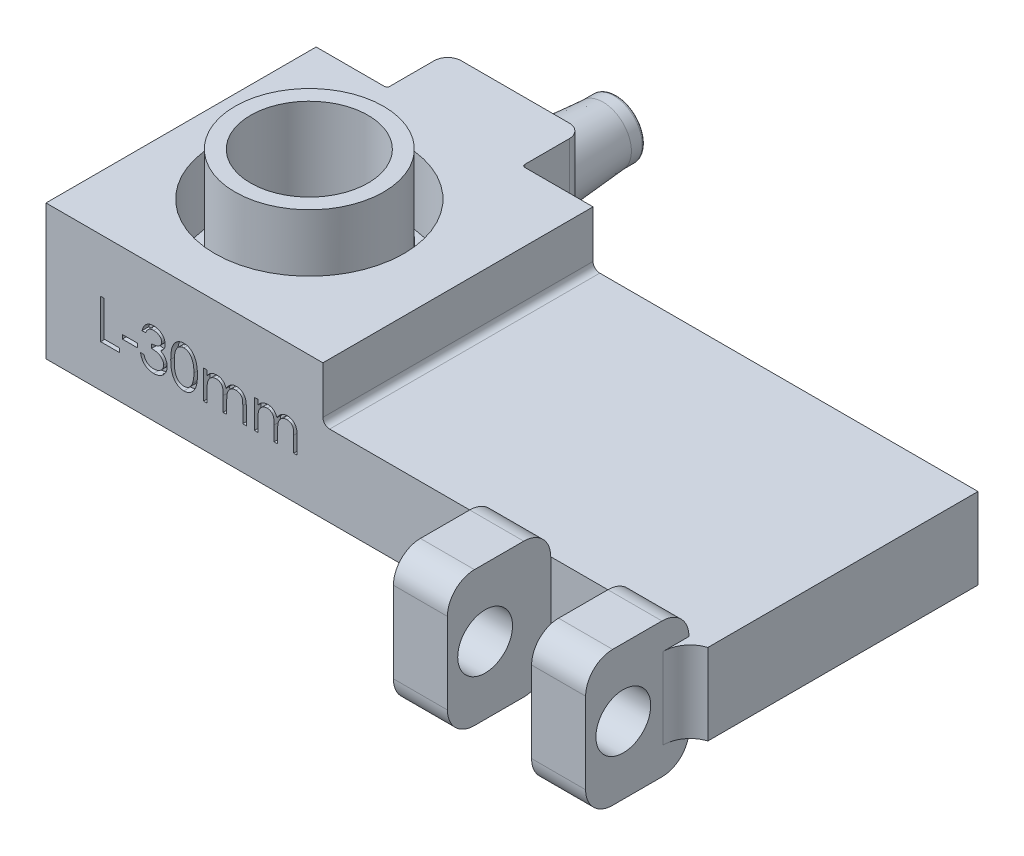
SolidWorks part; units mm, degrees
ref_plane "Front Plane" through (0, 0, 0) normal (0, 0, 1) x (1, 0, 0)
ref_plane "Top Plane" through (0, 0, 0) normal (0, 1, 0) x (1, 0, 0)
ref_plane "Right Plane" through (0, 0, 0) normal (1, 0, 0) x (0, 0, -1)
sketch "Sketch2" plane through (0, 0, 0) normal (0, 1, 0) x (1, 0, 0)
  line L1 (-14.4231, 13.5577) -> (34.5769, 13.5577)
  line L2 (-14.4231, 13.5577) -> (-14.4231, -6.4423)
  line L3 (-14.4231, -6.4423) -> (34.5769, -6.4423)
  line L4 (34.5769, 13.5577) -> (34.5769, -6.4423)
  dimension "D1" = 49
  dimension "D2" = 20
extrude "Boss-Extrude1" add sketch "Sketch2" along normal blind 10
sketch "Sketch3" plane through (0, 0, 0) normal (0, -1, 0) x (1, 0, 0)
  line L0 (34.5769, 6.4423) -> (34.5769, -13.5577) construction
  line L1 (27.5769, -5.0677) -> (-2.4231, -5.0677)
  line L2 (27.5769, -5.0677) -> (27.5769, -2.0477)
  line L3 (27.5769, -2.0477) -> (-2.4231, -2.0477)
  line L4 (-2.4231, -5.0677) -> (-2.4231, -2.0477)
  line L5 (-14.4231, -3.5577) -> (34.5769, -3.5577) construction
  line L6 (-14.4231, -13.5577) -> (-14.4231, 6.4423) construction
  dimension "D1" = 30
  dimension "D2" = 7
  dimension "D3" = 3.02
  dimension "D4" = 1.51
extrude "Cut-Extrude1" cut sketch "Sketch3" against normal blind 2
sketch "Sketch4" plane through (0, 0, 0) normal (0, -1, 0) x (1, 0, 0)
  line L0 (-2.4231, -2.0477) -> (-2.4231, -5.0677) construction
  line L1 (-2.4231, -6.0477) -> (-7.4231, -6.0477)
  line L2 (-2.4231, -6.0477) -> (-2.4231, -1.0477)
  line L3 (-2.4231, -1.0477) -> (-7.4231, -1.0477)
  line L4 (-7.4231, -6.0477) -> (-7.4231, -1.0477)
  line L6 (27.5769, -2.0477) -> (-2.4231, -2.0477) construction
  dimension "D1" = 5
  dimension "D2" = 5
  dimension "D3" = 1
extrude "Cut-Extrude2" cut sketch "Sketch4" against normal blind 5
sketch "Sketch5" plane through (0, 5, 0) normal (0, -1, 0) x (1, 0, 0)
  line L0 (-7.4231, -3.5477) -> (-2.4231, -3.5577) construction
  line L1 (-7.4231, -1.0477) -> (-7.4231, -6.0477) construction
  line L2 (-2.4231, -2.0477) -> (-2.4231, -5.0677) construction
  circle A0 centre (-4.9231, -3.5527) radius 7
  dimension "D1" = 14
extrude "Cut-Extrude3" cut sketch "Sketch5" against normal through all
sketch "Sketch6" plane through (0, 5, 0) normal (0, 1, 0) x (1, 0, 0)
  line L0 (-4.0731, 1.0477) -> (-2.4231, 1.0477)
  line L1 (-7.4231, 6.0477) -> (-5.7731, 6.0477)
  line L2 (-7.4231, 6.0477) -> (-7.4231, 1.0477)
  line L3 (-7.4231, 1.0477) -> (-5.7731, 1.0477)
  line L4 (-2.4231, 6.0477) -> (-2.4231, 1.0477)
  line L5 (-4.0731, 6.0477) -> (-2.4231, 6.0477)
  line L7 (-5.7731, 6.0477) -> (-5.7731, 1.0477)
  line L9 (-4.0731, 6.0477) -> (-4.0731, 1.0477)
  dimension "D1" = 1.7
extrude "Boss-Extrude2" add sketch "Sketch6" against normal blind 0.5
sketch "Sketch11" plane through (0, 0, 0) normal (0, -1, 0) x (1, 0, 0)
  circle A0 centre (28.8884, -3.5577) radius 2
  dimension "D1" = 4
extrude "Cut-Extrude4" cut sketch "Sketch11" against normal up to surface (2 mm away) up to face at (12.5769, 2, -3.5577)
sketch "Sketch12" plane through (0, 0, 0) normal (0, -1, 0) x (1, 0, 0)
  line L1 (-7.4231, -1.0477) -> (-2.4231, -1.0477)
  line L2 (-7.4231, -1.0477) -> (-7.4231, -6.0477)
  line L3 (-7.4231, -6.0477) -> (-2.4231, -6.0477)
  line L4 (-2.4231, -1.0477) -> (-2.4231, -6.0477)
extrude "Boss-Extrude4" add sketch "Sketch12" against normal blind 0.8
sketch "Sketch14" plane through (0, 0, 6.4423) normal (0, 0, 1) x (1, 0, 0)
  line L0 (-14.4231, 10) -> (34.5769, 10) construction
  line L1 (6.0769, 10) -> (34.5769, 10)
  line L2 (6.0769, 10) -> (6.0769, 6)
  line L3 (6.0769, 6) -> (34.5769, 6)
  line L4 (34.5769, 10) -> (34.5769, 6)
  line L5 (34.5769, 10) -> (34.5769, 0) construction
  line L6 (27.5769, 2) -> (-2.4231, 2) construction
  line L7 (2.0769, 5) -> (2.0769, 10) construction
  dimension "D1" = 4
  dimension "D2" = 4
extrude "Cut-Extrude6" cut sketch "Sketch14" against normal through all
fillet "Fillet1" radius 0.5 1 edges at (6.0769, 6, -3.5577)
sketch "Sketch13" plane through (0, 0, 6.4423) normal (0, 0, 1) x (1, 0, 0)
  line L0 (-10.748, 3.1258) -> (12.5164, 3.1258) construction
  text T0 "L-30mm" font "Century Gothic" height in points 11
extrude "Cut-Extrude5" cut sketch "Sketch13" against normal blind 0.5
sketch "Sketch19" plane through (0, 10, 0) normal (0, 1, 0) x (1, 0, 0)
  line L0 (6.0769, 13.5577) -> (-14.4231, 13.5577) construction
  line L1 (-9.1731, 18.0477) -> (0.8269, 18.0477)
  line L2 (-9.1731, 18.0477) -> (-9.1731, 13.5577)
  line L3 (-9.1731, 13.5577) -> (0.8269, 13.5577)
  line L4 (0.8269, 18.0477) -> (0.8269, 13.5577)
  line L6 (-4.1731, -6.4423) -> (-4.1731, 18.0477) construction
  line L8 (-14.4231, -6.4423) -> (6.0769, -6.4423) construction
  dimension "D1" = 10
  dimension "D3" = 12
extrude "Boss-Extrude5" add sketch "Sketch19" against normal up to surface (10 mm away) up to face at (13.4048, 0, -3.5577)
fillet "Fillet2" radius 1 2 edges at (-9.1731, 5, -18.0477) (0.8269, 5, -18.0477)
sketch "Sketch20" plane through (0, 0, -18.0477) normal (0, 0, -1) x (-1, 0, 0)
  line L0 (8.1731, 0) -> (0.1731, 0) construction
  circle A0 centre (4.6731, 3.5) radius 0.5
  dimension "D1" = 1
  dimension "D2" = 3.5
extrude "Cut-Extrude7" cut sketch "Sketch20" against normal up to next
sketch "Sketch21" plane through (0, 0, -18.0477) normal (0, 0, -1) x (-1, 0, 0)
  circle A0 centre (4.6731, 3.5) radius 1.4
  dimension "D1" = 2.8
extrude "Cut-Extrude8" cut sketch "Sketch21" against normal offset from surface (10 mm away) 2 up to face at (-5.1731, 3.5, -6.0477)
ref_axis "Axis1" through (-4.6731, 3.5, -8.0477) along (0, 0, -1)
ref_plane "Plane1" through (0, 3.5, 0) normal (0, -1, 0) x (-1, 0, 0)
sketch "Sketch23" plane through (0, 3.5, 0) normal (0, -1, 0) x (-1, 0, 0)
  line L0 (4.6731, 15.6131) -> (4.6731, 26.4829) construction
  line L1 (4.6731, 8.0477) -> (4.6731, 18.0477) construction
  line L2 (6.2731, 26.0477) -> (6.7731, 26.0477)
  line L3 (6.7731, 26.0477) -> (6.7731, 25.0477)
  line L4 (6.7731, 25.0477) -> (7.1731, 20.1558)
  line L5 (7.0734, 20.0477) -> (6.7731, 20.0477)
  line L6 (6.7731, 20.0477) -> (6.7731, 18.0477)
  line L7 (8.1731, 18.0477) -> (0.1731, 18.0477) construction
  line L8 (6.7731, 18.0477) -> (6.2731, 18.0477)
  line L9 (6.2731, 18.0477) -> (6.2731, 26.0477)
  arc A0 (7.0734, 20.0477) -> (7.1731, 20.1558) centre (7.0734, 20.1477) ccw
  dimension "D1" = 0.1
  dimension "D2" = 0.5
  dimension "D3" = 4.2
  dimension "D4" = 5
  dimension "D5" = 8
  dimension "D6" = 7
  dimension "D7" = 5
revolve "Revolve1" add sketch "Sketch23" angle 360 about L0
fillet "Fillet3" radius 0.2 5 edges at (-3.0731, 3.5, -26.0477) (-2.5731, 3.5, -26.0477) (-6.7731, 3.5, -18.0477)
sketch "Sketch24" plane through (0, 5, 0) normal (0, 1, 0) x (1, 0, 0)
  line L5 (-5.7731, 1.0477) -> (-5.7731, 6.0477) construction
  line L6 (-4.0731, 1.0477) -> (-5.7731, 1.0477)
  line L7 (-4.0731, 1.0477) -> (-4.0731, 4.0477)
  line L8 (-4.0731, 4.0477) -> (-5.7731, 4.0477)
  line L9 (-5.7731, 1.0477) -> (-5.7731, 4.0477)
  dimension "D1" = 3
extrude "Boss-Extrude6" add sketch "Sketch24" against normal up to vertex (0.5 mm away) up to point (-5.7731, 4.5, -1.0477)
sketch "Sketch29" plane through (0, 6, 0) normal (0, 1, 0) x (1, 0, 0)
  line L0 (29.0269, 16.5533) -> (29.0269, -8.2906) construction
  line L1 (34.5769, 13.5577) -> (34.5769, -6.4423) construction
  line L2 (23.0969, 16.5533) -> (23.0969, -8.2906) construction
  dimension "D1" = 5.55
  dimension "D2" = 5.93
sketch "Sketch31" plane through (0, 0, 6.4423) normal (0, 0, 1) x (1, 0, 0)
  line L0 (29.0269, 7.2512) -> (29.0269, -2.1723) construction
  line L1 (29.1769, 8) -> (33.1769, 8)
  line L2 (29.1769, 8) -> (29.1769, -2)
  line L3 (29.1769, -2) -> (33.1769, -2)
  line L4 (33.1769, 8) -> (33.1769, -2)
  line L5 (29.1769, 8) -> (33.1769, -2) construction
  line L6 (29.1769, -2) -> (33.1769, 8) construction
  line L7 (23.0969, 7.2512) -> (23.0969, -2.1723) construction
  line L8 (34.5769, 6) -> (34.5769, 0) construction
  line L9 (34.5769, 3) -> (13.2124, 3) construction
  line L10 (18.9469, 8) -> (22.9469, 8)
  line L11 (18.9469, 8) -> (18.9469, -2)
  line L12 (18.9469, -2) -> (22.9469, -2)
  line L13 (22.9469, 8) -> (22.9469, -2)
  line L14 (18.9469, 8) -> (22.9469, -2) construction
  line L15 (18.9469, -2) -> (22.9469, 8) construction
  point P0 (31.1769, 3)
  point P11 (20.9469, 3)
  dimension "D1" = 4
  dimension "D2" = 10
  dimension "D3" = 5.55
  dimension "D4" = 5.93
  dimension "D5" = 0.15
  dimension "D6" = 4
  dimension "D7" = 10
  dimension "D8" = 0.15
extrude "Boss-Extrude9" add sketch "Sketch31" along normal blind 7.65
sketch "Sketch33" plane through (33.1769, 0, 0) normal (1, 0, 0) x (0, 0, -1)
  line L0 (-14.0923, -2) -> (-14.0923, 8) construction
  circle A0 centre (-11.3023, 3) radius 2.03
  dimension "D1" = 4.06
  dimension "D2" = 2.79
extrude "Cut-Extrude11" cut sketch "Sketch33" against normal up to surface (14.23 mm away) up to face at (18.9469, 3, 8.9923)
fillet "Fillet4" radius 2 8 edges at (31.1769, -2, 14.0923) (31.1769, -2, 6.4423) (20.9469, -2, 6.4423) (31.1769, 8, 6.4423) (31.1769, 8, 14.0923) (20.9469, -2, 14.0923) (20.9469, 8, 6.4423) (20.9469, 8, 14.0923)
fillet "Fillet5" radius 2 2 edges at (33.1769, 3, 6.4423) (18.9469, 3, 6.4423)
sketch "Sketch34" plane through (0, 5, 0) normal (0, 1, 0) x (1, 0, 0)
  circle A0 centre (-4.9231, 3.5527) radius 4.35
  circle A1 centre (-4.9231, 3.5527) radius 5.5
  dimension "D1" = 8.7
  dimension "D2" = 11
extrude "Boss-Extrude10" add sketch "Sketch34" along normal blind 8.2
